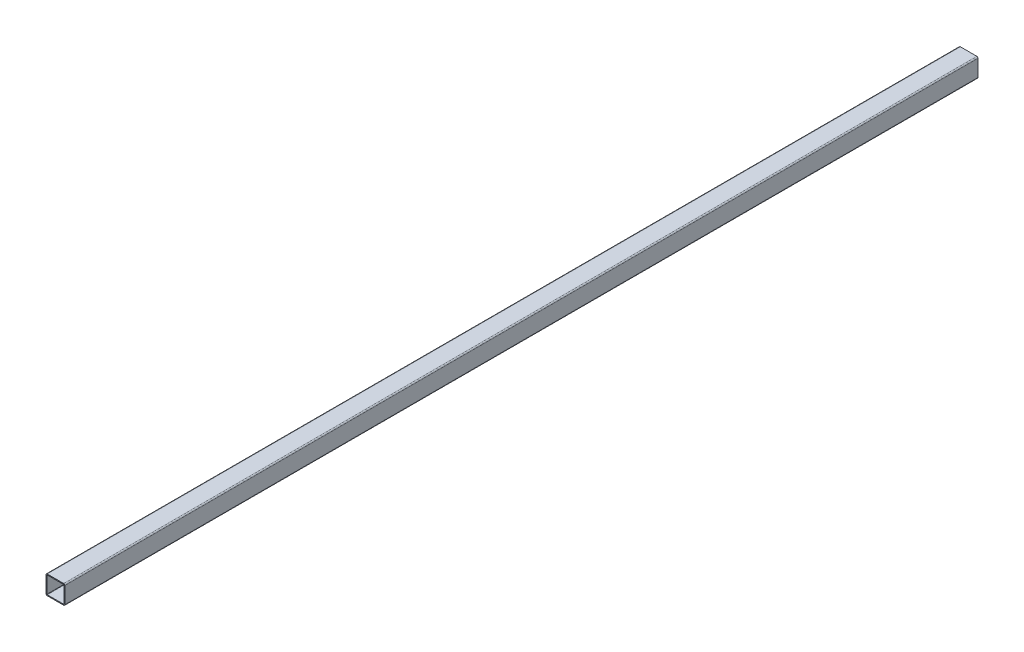
SolidWorks part; units mm, degrees
material "AISI 1010 Steel, hot rolled bar"
ref_plane "Front Plane" through (0, 0, 0) normal (0, 0, 1) x (1, 0, 0)
ref_plane "Top Plane" through (0, 0, 0) normal (0, 1, 0) x (1, 0, 0)
ref_plane "Right Plane" through (0, 0, 0) normal (1, 0, 0) x (0, 0, -1)
sketch "Sketch1" plane through (0, 0, 0) normal (0, 0, 1) x (1, 0, 0)
  line L0 (-14, 14.48) -> (14, 14.48)
  line L1 (-14, -16) -> (14, -16)
  line L2 (-16, -14) -> (-16, 14)
  line L3 (-14, 16) -> (14, 16)
  line L4 (16, -14) -> (16, 14)
  line L5 (-16, -16) -> (16, 16) construction
  line L6 (-16, 16) -> (16, -16) construction
  line L7 (14.48, -14) -> (14.48, 14)
  line L8 (-14, -14.48) -> (14, -14.48)
  line L9 (-14.48, -14) -> (-14.48, 14)
  arc A0 (14, -16) -> (16, -14) centre (14, -14) ccw
  arc A1 (-16, 14) -> (-14, 16) centre (-14, 14) cw
  arc A2 (-16, -14) -> (-14, -16) centre (-14, -14) ccw
  arc A3 (16, 14) -> (14, 16) centre (14, 14) ccw
  arc A4 (14.48, 14) -> (14, 14.48) centre (14, 14) ccw
  arc A5 (14, -14.48) -> (14.48, -14) centre (14, -14) ccw
  arc A6 (-14.48, -14) -> (-14, -14.48) centre (-14, -14) ccw
  arc A7 (-14.48, 14) -> (-14, 14.48) centre (-14, 14) cw
  point P0 (0, 0)
  dimension "D3" = 2
  dimension "D1" = 32
  dimension "D2" = 32
  dimension "D4" = 1.52
extrude "Boss-Extrude1" add sketch "Sketch1" along normal blind 774 and the other way blind 774
